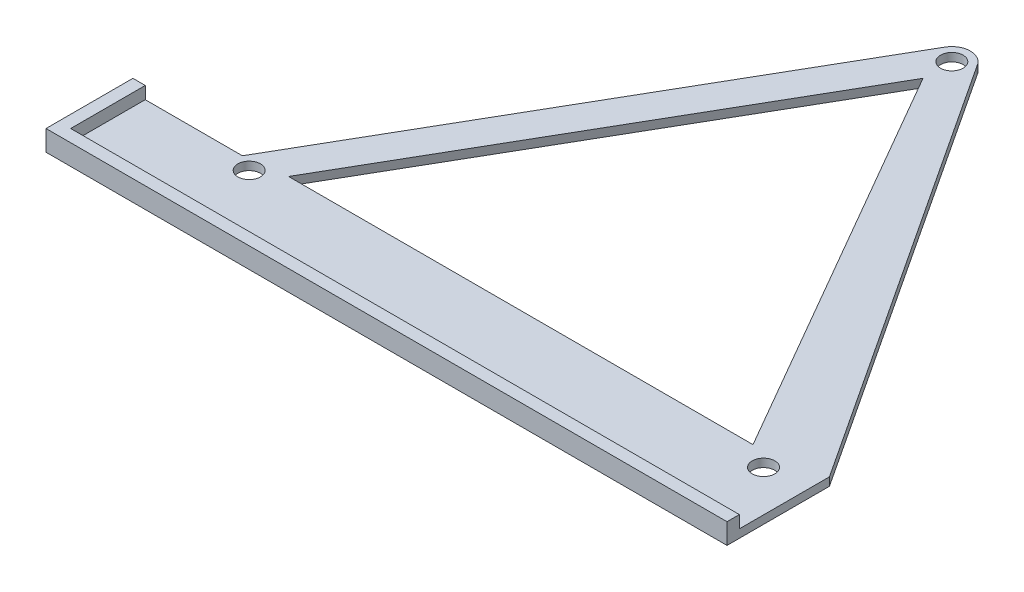
SolidWorks part; units mm, degrees
ref_plane "Front Plane" through (0, 0, 0) normal (0, 0, 1) x (1, 0, 0)
ref_plane "Top Plane" through (0, 0, 0) normal (0, 1, 0) x (1, 0, 0)
ref_plane "Right Plane" through (0, 0, 0) normal (1, 0, 0) x (0, 0, -1)
sketch "Sketch1" plane through (0, 0, 0) normal (0, 1, 0) x (1, 0, 0)
  line L0 (-62.5, -54.1266) -> (0, 54.1266) construction
  line L1 (0, 54.1266) -> (62.5, -54.1266) construction
  line L2 (62.5, -54.1266) -> (-62.5, -54.1266) construction
  line L5 (-3.8971, 56.3766) -> (-66.3971, -51.8766)
  line L6 (72.5, -48.1157) -> (3.8971, 56.3766)
  line L11 (-93, -73) -> (72.5, -73)
  line L17 (0, 54.1266) -> (0, 70) construction
  line L18 (0, -54.1266) -> (0, -70) construction
  line L19 (-93, -73) -> (72.5, -73)
  line L38 (-66.3971, -51.8766) -> (-90, -51.8766)
  line L39 (-90, -51.8766) -> (-93, -51.8766)
  line L40 (-93, -51.8766) -> (-93, -73)
  line L41 (72.5, -70) -> (-90, -70)
  line L42 (-90, -51.8766) -> (-90, -70)
  line L43 (-56.4378, -50.6266) -> (0, 47.1266)
  line L44 (72.5, -73) -> (72.5, -70)
  line L45 (72.5, -48.1157) -> (72.5, -70)
  line L46 (0, 47.1266) -> (56.4378, -50.6266)
  line L47 (56.4378, -50.6266) -> (-56.4378, -50.6266)
  line L49 (-90, -70) -> (90, -70) construction
  line L50 (-90, -70) -> (-90, 70) construction
  line L51 (-90, 70) -> (90, 70) construction
  line L52 (90, -70) -> (90, 70) construction
  line L53 (-90, -70) -> (90, 70) construction
  line L54 (-90, 70) -> (90, -70) construction
  circle A0 centre (0, -18.0422) radius 36.0844 construction
  arc A1 (3.8971, 56.3766) -> (-3.8971, 56.3766) centre (0, 54.1266) ccw
  circle A4 centre (0, 54.1266) radius 2.75
  circle A5 centre (62.5, -54.1266) radius 2.75
  circle A6 centre (-62.5, -54.1266) radius 2.75
  point P10 (0, 0)
  point P31 (0, 70)
  dimension "D2" = 9
  dimension "D5" = 180
  dimension "D7" = 5.5
  dimension "D1" = 125
  dimension "D3" = 120
  dimension "D8" = 140
  dimension "D9" = 7
  dimension "D10" = 7
  dimension "D11" = 7
  dimension "D6" = 10
  dimension "D4" = 3
extrude "Boss-Extrude4" add sketch "Sketch1" along normal blind 2 contours L6 A1 L5 L38 L45 A6 A5 A4 region at (0, 0, -58.4193)
extrude "Boss-Extrude7" add sketch "Sketch1<6>" along normal blind 5 contours L11 L44 L39 L40 region at (-18.2693, 0, 70.4576)
sketch "Sketch1<6>" plane through (0, 0, 0) normal (0, 1, 0) x (1, 0, 0) same geometry as "Sketch1"
